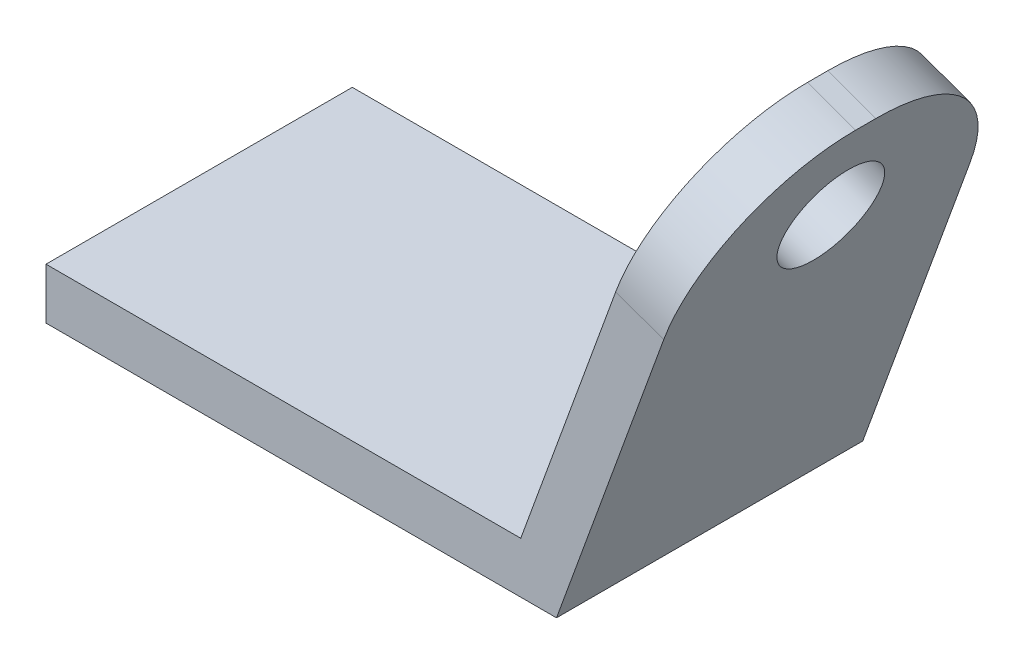
SolidWorks part; units mm, degrees
ref_plane "Front Plane" through (0, 0, 0) normal (0, 0, 1) x (1, 0, 0)
ref_plane "Top Plane" through (0, 0, 0) normal (0, 1, 0) x (1, 0, 0)
ref_plane "Right Plane" through (0, 0, 0) normal (1, 0, 0) x (0, 0, -1)
sketch "Sketch1" plane through (0, 0, 0) normal (0, 1, 0) x (1, 0, 0)
  line L1 (-31.75, -19.05) -> (31.75, -19.05)
  line L2 (-31.75, -19.05) -> (-31.75, 19.05)
  line L3 (-31.75, 19.05) -> (31.75, 19.05)
  line L4 (31.75, -19.05) -> (31.75, 19.05)
  line L5 (-31.75, -19.05) -> (31.75, 19.05) construction
  line L6 (-31.75, 19.05) -> (31.75, -19.05) construction
  point P0 (0, 0)
  dimension "D1" = 63.5
  dimension "D2" = 38.1
extrude "Boss-Extrude1" add sketch "Sketch1" along normal blind 6.35
sketch "Sketch2" plane through (0, 0, 19.05) normal (0, 0, 1) x (1, 0, 0)
  line L0 (31.75, 0) -> (51.1655, 53.3436)
  line L1 (31.75, 0) -> (25.783, 2.1718)
  line L2 (51.1655, 53.3436) -> (45.1984, 55.5154)
  line L3 (25.783, 2.1718) -> (45.1984, 55.5154)
  line L4 (31.75, 0) -> (45.1984, 55.5154) construction
  line L5 (51.1655, 53.3436) -> (25.783, 2.1718) construction
  line L6 (31.75, 6.35) -> (31.75, 0) construction
  line L7 (-31.75, 0) -> (31.75, 0) construction
  point P1 (38.4742, 27.7577)
  dimension "D1" = 20
  dimension "D2" = 50.8
extrude "Boss-Extrude2" add sketch "Sketch2" against normal up to surface (38.1 mm away) up to face at (0, 3.175, -19.05)
sketch "Sketch3" plane through (22.0689, -8.0324, 0) normal (-0.9397, 0.342, 0) x (0, 0, 1)
  line L0 (0, 54.9262) -> (0, 67.6262) construction
  line L1 (-19.05, 67.6262) -> (19.05, 67.6262) construction
  circle A0 centre (0, 54.9262) radius 6.35
  dimension "D2" = 12.7
  dimension "D1" = 12.7
extrude "Cut-Extrude1" cut sketch "Sketch3" against normal through all
fillet "Fillet1" radius 17.78 2 edges at (48.1819, 54.4295, 19.05) (48.1819, 54.4295, -19.05)
